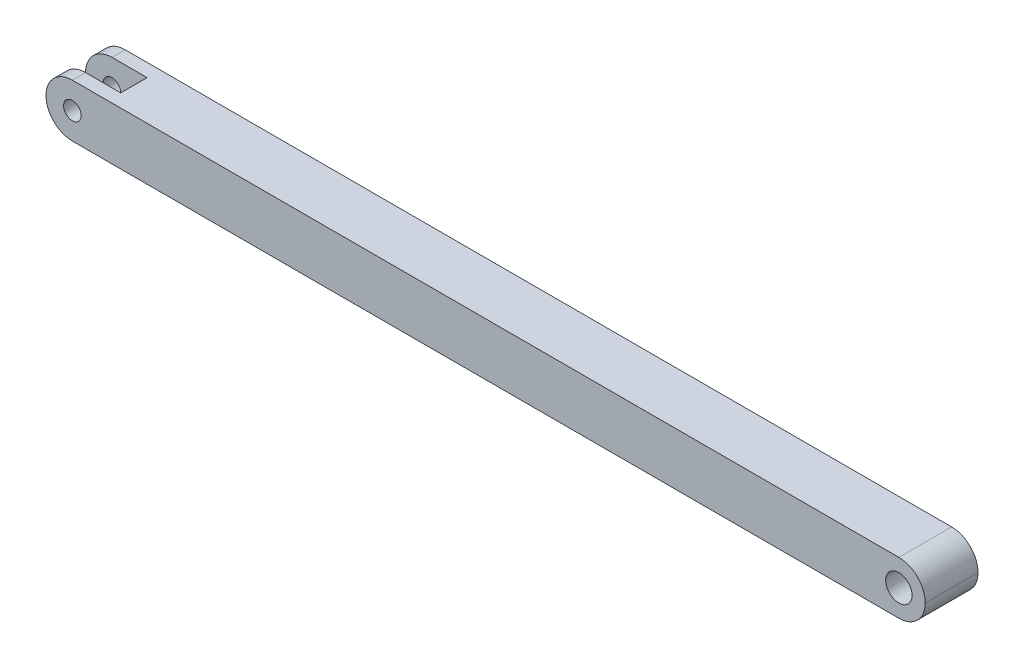
SolidWorks part; units mm, degrees
material "6061 Alloy"
ref_plane "Front Plane" through (0, 0, 0) normal (0, 0, 1) x (1, 0, 0)
ref_plane "Top Plane" through (0, 0, 0) normal (0, 1, 0) x (1, 0, 0)
ref_plane "Right Plane" through (0, 0, 0) normal (1, 0, 0) x (0, 0, -1)
sketch "Sketch1" plane through (0, 0, 0) normal (0, 0, 1) x (1, 0, 0)
  line L0 (0, 0) -> (0, 30)
  line L1 (0, 30) -> (500, 30)
  line L2 (500, 30) -> (500, 0)
  line L3 (500, 0) -> (0, 0)
  dimension "D1" = 30
  dimension "D2" = 500
extrude "Boss-Extrude1" add sketch "Sketch1" along normal mid plane 30
sketch "Sketch2" plane through (0, 30, 0) normal (0, 1, 0) x (1, 0, 0)
  line L0 (0, -7.5) -> (0, 7.5)
  line L1 (0, -15) -> (0, 15) construction
  line L2 (0, 7.5) -> (35, 7.5)
  line L3 (35, 7.5) -> (35, -7.5)
  line L4 (35, -7.5) -> (0, -7.5)
  point P6 (0, 0)
  dimension "D1" = 15
  dimension "D2" = 35
extrude "Cut-Extrude1" cut sketch "Sketch2" against normal up to next
sketch "Sketch3" plane through (0, 0, 15) normal (0, 0, 1) x (1, 0, 0)
  line L0 (0, 15) -> (15, 15) construction
  line L1 (0, 30) -> (0, 0) construction
  line L2 (485, 15) -> (500, 15) construction
  line L3 (500, 0) -> (500, 30) construction
  line L4 (15, 15) -> (115, 15) construction
  circle A0 centre (15, 15) radius 5
  circle A1 centre (485, 15) radius 7.5
  dimension "D1" = 10
  dimension "D2" = 15
  dimension "D3" = 15
  dimension "D4" = 15
  dimension "D5" = 100
extrude "Cut-Extrude2" cut sketch "Sketch3" against normal through all both and the other way through all
fillet "Fillet3" radius 15 6 edges at (500, 0, 0) (500, 30, 0) (0, 0, 11.25) (0, 0, -11.25) (0, 30, -11.25) (0, 30, 11.25)
sketch "Sketch4" plane through (0, 30, 0) normal (0, 1, 0) x (1, 0, 0)
  line L0 (435, 15) -> (435, 3)
  line L1 (485, 15) -> (15, 15) construction
  line L2 (435, 3) -> (285, 3)
  line L3 (285, 3) -> (285, 15)
  line L4 (285, 15) -> (435, 15)
  line L5 (485, -15) -> (485, 15) construction
  dimension "D1" = 12
  dimension "D2" = 150
  dimension "D3" = 50
extrude "Cut-Extrude3" [suppressed] cut sketch "Sketch4" against normal through all both and the other way through all
